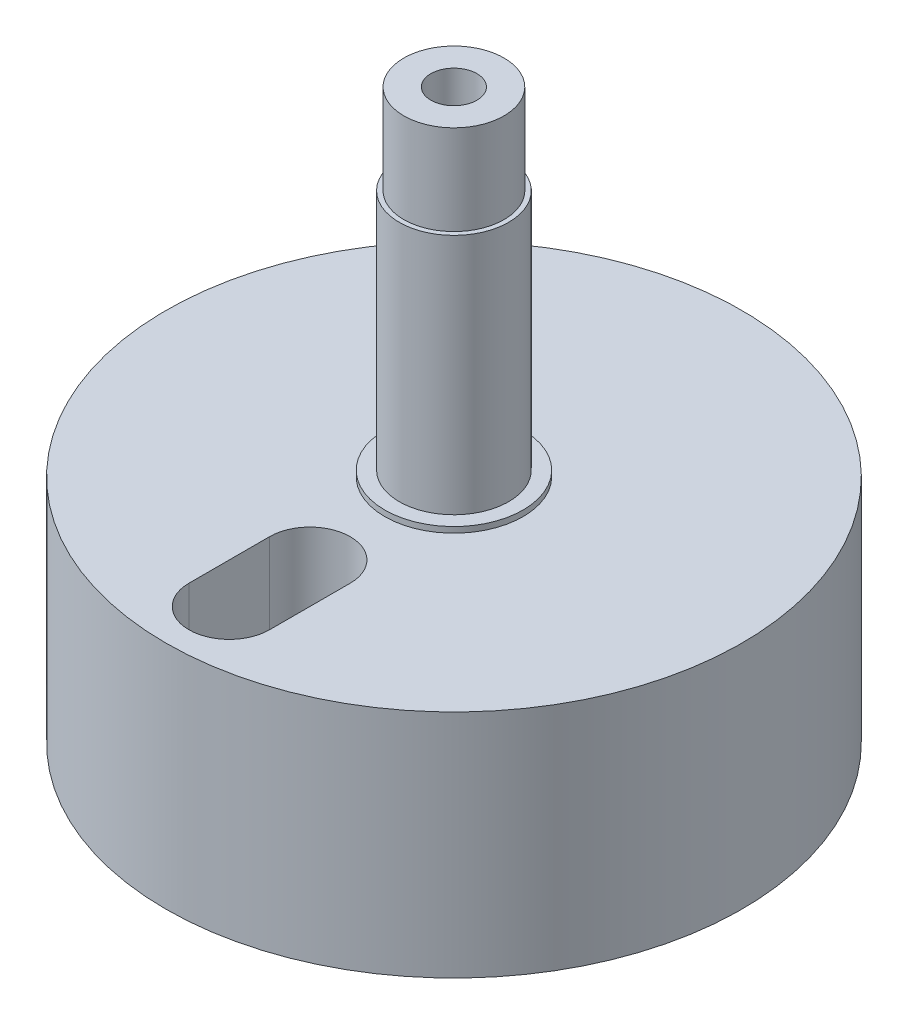
SolidWorks part; units mm, degrees
ref_plane "Front Plane" through (0, 0, 0) normal (0, 0, 1) x (1, 0, 0)
ref_plane "Top Plane" through (0, 0, 0) normal (0, 1, 0) x (1, 0, 0)
ref_plane "Right Plane" through (0, 0, 0) normal (1, 0, 0) x (0, 0, -1)
sketch "Sketch1" plane through (0, 0, 0) normal (0, 1, 0) x (1, 0, 0)
  circle A0 centre (0, 0) radius 25
  dimension "D1" = 50
extrude "Boss-Extrude1" add sketch "Sketch1" along normal blind 20
sketch "Sketch3" plane through (0, 20, 0) normal (0, 1, 0) x (1, 0, 0)
  line L0 (-3.5, -12.5) -> (-3.5, -19.5)
  line L1 (3.5, -12.5) -> (3.5, -19.5)
  line L2 (-3.5, -16) -> (3.5, -16) construction
  arc A0 (3.5, -12.5) -> (-3.5, -12.5) centre (0, -12.5) ccw
  arc A1 (-3.5, -19.5) -> (3.5, -19.5) centre (0, -19.5) ccw
  point P7 (0, -16)
  dimension "D1" = 7
  dimension "D2" = 7
  dimension "D3" = 12.5
extrude "Cut-Extrude2" cut sketch "Sketch3" against normal blind 10
sketch "Sketch5" plane through (0, 10, 0) normal (0, 1, 0) x (1, 0, 0)
  circle A0 centre (0, -16) radius 2
  point P2 (0, -16)
  dimension "D1" = 4
extrude "Cut-Extrude3" cut sketch "Sketch5" against normal through all
sketch "Sketch2" plane through (0, 20, 0) normal (0, 1, 0) x (1, 0, 0)
  circle A0 centre (0, 0) radius 25
  circle A1 centre (0, 0) radius 6
  dimension "D1" = 50
  dimension "D2" = 12
extrude "Boss-Extrude2" add sketch "Sketch2" along normal blind 0.5 contours A1
sketch "Sketch7" plane through (0, 20.5, 0) normal (0, 1, 0) x (1, 0, 0)
  circle A0 centre (0, 0) radius 4.75
  dimension "D1" = 9.5
extrude "Boss-Extrude3" add sketch "Sketch7" along normal blind 21
sketch "Sketch8" plane through (0, 41.5, 0) normal (0, 1, 0) x (1, 0, 0)
  circle A0 centre (0, 0) radius 4.35
  dimension "D1" = 8.7
extrude "Boss-Extrude4" add sketch "Sketch8" along normal blind 7.8
sketch "Sketch6" plane through (0, 0, 0) normal (0, -1, 0) x (1, 0, 0)
  circle A0 centre (0, 0) radius 2
  dimension "D1" = 4
extrude "Cut-Extrude4" cut sketch "Sketch6" against normal through all
